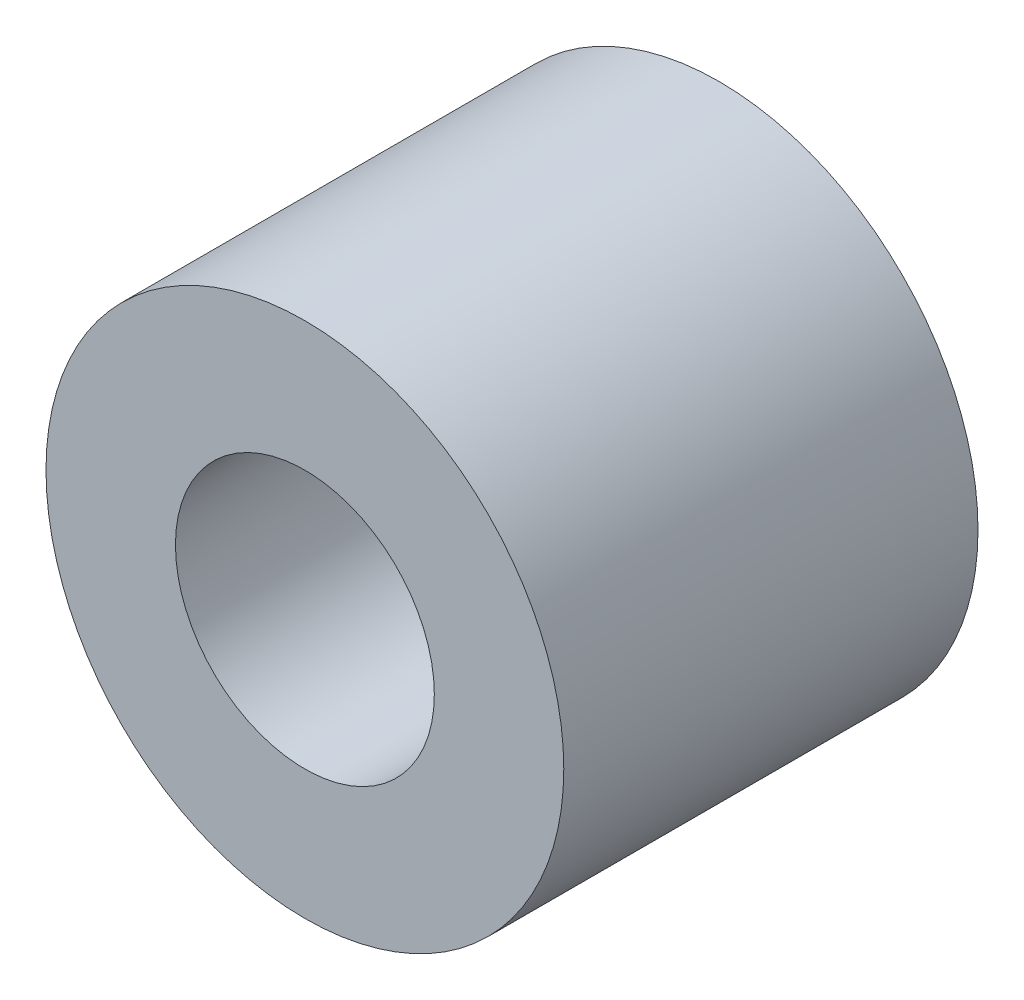
SolidWorks part; units mm, degrees
ref_plane "Front Plane" through (0, 0, 0) normal (0, 0, 1) x (1, 0, 0)
ref_plane "Top Plane" through (0, 0, 0) normal (0, 1, 0) x (1, 0, 0)
ref_plane "Right Plane" through (0, 0, 0) normal (1, 0, 0) x (0, 0, -1)
sketch "Sketch1" plane through (0, 0, 0) normal (1, 0, 0) x (0, 0, -1)
  line L0 (0, 985.393) -> (180.975, 985.393) construction
  line L1 (123.825, 1017.143) -> (101.6, 1017.143) construction
  line L6 (104.775, 1001.268) -> (155.575, 1001.268)
  line L7 (104.775, 1001.268) -> (104.775, 1017.143)
  line L8 (104.775, 1017.143) -> (155.575, 1017.143)
  line L9 (155.575, 1001.268) -> (155.575, 1017.143)
  line L10 (104.775, 1001.268) -> (180.975, 1001.268) construction
  line L11 (180.975, 1001.268) -> (180.975, 969.518) construction
  point P20 (155.575, 1009.2055)
  dimension "D1" = 25.4
revolve "Revolve1" add sketch "Sketch1" angle 360 about L0
